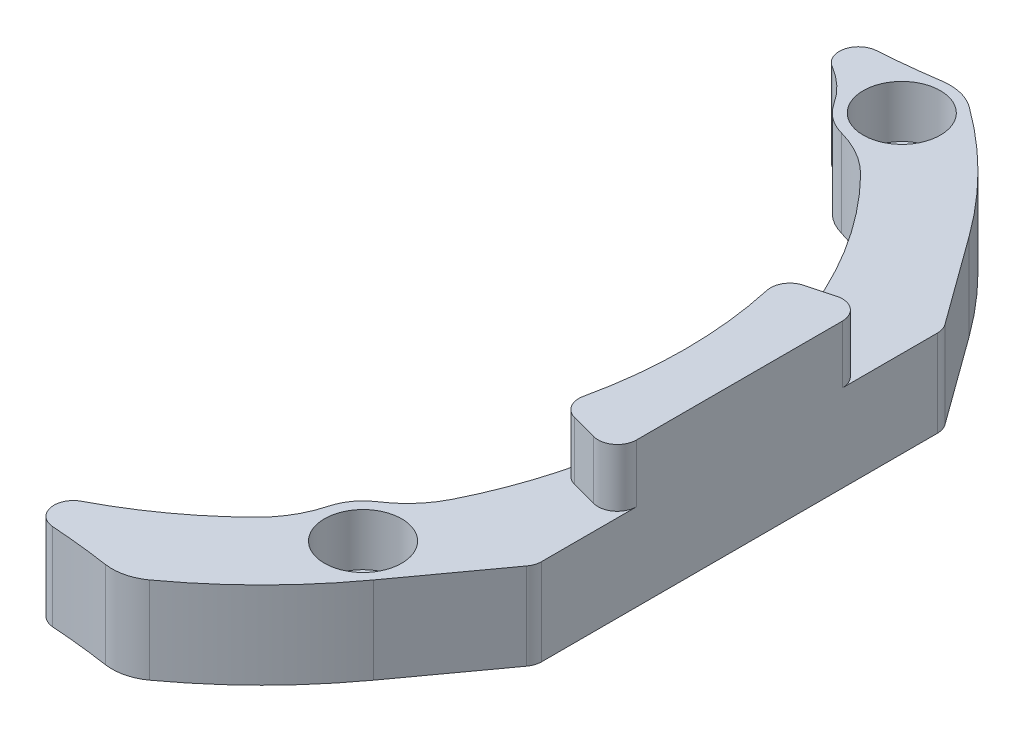
SolidWorks part; units mm, degrees
material "6061 合金"
ref_plane "前视基准面" through (0, 0, 0) normal (0, 0, 1) x (1, 0, 0)
ref_plane "上视基准面" through (0, 0, 0) normal (0, 1, 0) x (1, 0, 0)
ref_plane "右视基准面" through (0, 0, 0) normal (1, 0, 0) x (0, 0, -1)
other "Configuration Table"
sketch "草图1" plane through (0, 0, 0) normal (0, 1, 0) x (1, 0, 0)
  line L0 (0, 0) -> (36.1587, 0) construction
  arc A161 (21.6874, 13.5954) -> (21.2367, 15.4294) centre (19.2142, 13.9599) ccw construction
  arc A162 (21.6874, 13.5954) -> (21.5774, 2.7345) centre (61.26, 7.7635) ccw construction
  arc A163 (2.7345, 21.5774) -> (7.7635, 21.26) centre (7.7635, 61.26) ccw construction
  arc A164 (7.7635, 21.26) -> (13.5954, 21.6874) centre (7.7635, 61.26) ccw construction
  arc A165 (15.4294, 21.2367) -> (13.5954, 21.6874) centre (13.9599, 19.2142) ccw construction
  arc A166 (21.2367, 15.4294) -> (15.4294, 21.2367) centre (0, 0) ccw construction
  arc A167 (21.6874, 13.5954) -> (21.2367, 15.4294) centre (19.2142, 13.9599) ccw
  arc A168 (21.6874, 13.5954) -> (21.3486, 5.1029) centre (61.26, 7.7635) ccw
  arc A169 (5.1029, 21.3486) -> (7.7635, 21.26) centre (7.7635, 61.26) ccw
  arc A170 (7.7635, 21.26) -> (13.5954, 21.6874) centre (7.7635, 61.26) ccw
  arc A171 (15.4294, 21.2367) -> (13.5954, 21.6874) centre (13.9599, 19.2142) ccw
  arc A172 (21.2367, 15.4294) -> (15.4294, 21.2367) centre (0, 0) ccw
  circle A184 centre (13.9599, 19.2142) radius 1.025
  arc A212 (19.655, -9.7715) -> (15.6735, 15.367) centre (0, 0) ccw
  arc A213 (15.6735, 15.367) -> (13.302, 16.7505) centre (11.9604, 11.7265) ccw
  arc A214 (11.8201, 17.8271) -> (13.302, 16.7505) centre (13.9599, 19.2142) ccw
  arc A215 (11.8201, 17.8271) -> (9.7715, 19.655) centre (7.4566, 14.9987) ccw
  arc A216 (9.7715, 19.655) -> (-15.367, 15.6735) centre (0, 0) ccw
  arc A217 (21.3486, 5.1029) -> (15.6735, 15.367) centre (0, 0) ccw
  arc A218 (15.6735, 15.367) -> (13.302, 16.7505) centre (11.9604, 11.7265) ccw
  arc A219 (11.8201, 17.8271) -> (13.302, 16.7505) centre (13.9599, 19.2142) ccw
  arc A220 (11.8201, 17.8271) -> (9.7715, 19.655) centre (7.4566, 14.9987) ccw
  arc A221 (9.7715, 19.655) -> (5.1029, 21.3486) centre (0, 0) ccw
  arc A249 (13.5954, -21.6874) -> (13.9599, -21.7142) centre (13.9599, -19.2142) ccw construction
  arc A250 (13.5954, -21.6874) -> (2.7345, -21.5774) centre (7.7635, -61.26) ccw construction
  arc A251 (13.9599, -21.7142) -> (15.4294, -21.2367) centre (13.9599, -19.2142) ccw construction
  arc A252 (15.4294, -21.2367) -> (21.2367, -15.4294) centre (0, 0) ccw construction
  arc A253 (21.2367, -15.4294) -> (21.6874, -13.5954) centre (19.2142, -13.9599) ccw construction
  arc A254 (19.655, -9.7715) -> (15.6735, 15.367) centre (0, 0) ccw
  arc A255 (0, -21.95) -> (15.367, -15.6735) centre (0, 0) ccw
  arc A256 (15.367, -15.6735) -> (16.7505, -13.302) centre (11.7265, -11.9604) ccw
  arc A257 (17.8271, -11.8201) -> (16.7505, -13.302) centre (19.2142, -13.9599) ccw
  arc A258 (17.8271, -11.8201) -> (19.655, -9.7715) centre (14.9987, -7.4566) ccw
  arc A259 (19.655, -9.7715) -> (21.3486, -5.1029) centre (0, 0) ccw
  arc A260 (5.1029, -21.3486) -> (15.367, -15.6735) centre (0, 0) ccw
  arc A261 (15.367, -15.6735) -> (16.7505, -13.302) centre (11.7265, -11.9604) ccw
  arc A262 (17.8271, -11.8201) -> (16.7505, -13.302) centre (19.2142, -13.9599) ccw
  arc A263 (17.8271, -11.8201) -> (19.655, -9.7715) centre (14.9987, -7.4566) ccw
  arc A264 (21.5774, -2.7345) -> (21.6874, -13.5954) centre (61.26, -7.7635) ccw construction
  arc A265 (13.5954, -21.6874) -> (13.9599, -21.7142) centre (13.9599, -19.2142) ccw
  arc A266 (13.5954, -21.6874) -> (5.1029, -21.3486) centre (7.7635, -61.26) ccw
  arc A267 (13.9599, -21.7142) -> (15.4294, -21.2367) centre (13.9599, -19.2142) ccw
  arc A268 (15.4294, -21.2367) -> (21.2367, -15.4294) centre (0, 0) ccw
  arc A269 (21.2367, -15.4294) -> (21.6874, -13.5954) centre (19.2142, -13.9599) ccw
  arc A270 (21.3486, -5.1029) -> (21.6874, -13.5954) centre (61.26, -7.7635) ccw
  arc A271 (19.2142, -15.4099) -> (19.2142, -12.5099) centre (19.2142, -13.9599) ccw construction
  arc A272 (19.2142, -12.5099) -> (19.2142, -15.4099) centre (19.2142, -13.9599) ccw construction
  arc A273 (19.2142, -15.4099) -> (19.2142, -12.5099) centre (19.2142, -13.9599) ccw
  arc A274 (19.2142, -12.5099) -> (19.2142, -15.4099) centre (19.2142, -13.9599) ccw
  arc A275 (21.3486, 5.1029) -> (15.6735, 15.367) centre (0, 0) ccw
  dimension "D1" = 2.05
  dimension "D2" = 0.2
  dimension "D3" = 0.2
extrude "凸台-拉伸1" add sketch "草图1" along normal blind 4.5 contours A168 A167 A172 A171 A170 A169 A184 | A270 A259 A263 A262 A261 A260 A266 A265 A267 A268 A269 A274 A273 region at (16.4768, 0, -16.3777) region at (16.2264, 0, 16.6111)
sketch "草图4" plane through (0, 4.5, 0) normal (0, 1, 0) x (1, 0, 0)
  line L0 (0, 0) -> (32.7858, 0) construction
  line L1 (21.2367, -15.4294) -> (24.7634, -10.5753)
  line L2 (24.7634, -10.5753) -> (24.7634, 10.5753)
  line L3 (21.2367, 15.4294) -> (24.7634, 10.5753)
  arc A0 (21.6874, 13.5954) -> (21.2367, 15.4294) centre (19.2142, 13.9599) ccw construction
  arc A1 (21.2367, -15.4294) -> (21.6874, -13.5954) centre (19.2142, -13.9599) ccw construction
  arc A2 (21.6874, 13.5954) -> (21.3486, 5.1029) centre (61.26, 7.7635) ccw construction
  arc A3 (19.655, -9.7715) -> (15.6735, 15.367) centre (0, 0) ccw
  arc A4 (21.3486, -5.1029) -> (21.3486, 5.1029) centre (0, 0) ccw
  arc A5 (21.3486, -5.1029) -> (21.6874, -13.5954) centre (61.26, -7.7635) ccw construction
  arc A6 (21.6874, 13.5954) -> (21.3486, 5.1029) centre (61.26, 7.7635) ccw
  arc A7 (21.3486, -5.1029) -> (21.6874, -13.5954) centre (61.26, -7.7635) ccw
  arc A9 (21.6874, 13.5954) -> (21.2367, 15.4294) centre (19.2142, 13.9599) ccw
  arc A10 (21.2367, -15.4294) -> (21.6874, -13.5954) centre (19.2142, -13.9599) ccw
  point P16 (24.7634, 0)
  dimension "D2" = 6
  dimension "D1" = 0.2
extrude "凸台-拉伸2" add sketch "草图4" against normal up to surface (4.5 mm away) up to face at (19.2142, 0, 15.4099)
sketch "草图5" plane through (0, 4.5, 0) normal (0, 1, 0) x (1, 0, 0)
  line L0 (0, 0) -> (29.9967, 0) construction
  line L1 (21.2021, -5.6811) -> (24.7634, -6.6353)
  line L2 (24.7634, -10.5753) -> (24.7634, 10.5753) construction
  line L3 (21.2021, 5.6811) -> (24.7634, 6.6353)
  line L4 (24.7634, -6.6353) -> (24.7634, 6.6353)
  arc A0 (19.655, -9.7715) -> (15.6735, 15.367) centre (0, 0) ccw construction
  arc A1 (21.2021, -5.6811) -> (21.2021, 5.6811) centre (0, 0) ccw
  dimension "D1" = 15
extrude "凸台-拉伸3" add sketch "草图5" along normal blind 3
sketch "草图6" plane through (0, 7.5, 0) normal (0, 1, 0) x (1, 0, 0)
  line L0 (24.7634, -6.6353) -> (18.3043, -4.9046)
  line L1 (24.7634, 6.6353) -> (18.3043, 4.9046)
  line L2 (24.7634, -6.6353) -> (24.7634, 6.6353)
  arc A2 (18.3043, -4.9046) -> (18.3043, 4.9046) centre (0, 0) ccw
  arc A3 (18.3043, -4.9046) -> (18.3043, 4.9046) centre (0, 0) ccw
  dimension "D1" = 3
extrude "凸台-拉伸4" [suppressed] add sketch "草图6" against normal blind 3
fillet "圆角2" [suppressed] radius 1
sketch "草图7" plane through (0, 4.5, 0) normal (0, 1, 0) x (1, 0, 0)
  circle A0 centre (19.2142, -13.9599) radius 1
  circle A1 centre (19.2142, -13.9599) radius 1.45 construction
  circle A2 centre (19.2142, -13.9599) radius 1.45
  dimension "D1" = 2
extrude "凸台-拉伸5" add sketch "草图7" against normal up to surface (4.5 mm away) up to face at (15.8728, 0, -1.0637)
hole_wizard "M2.5 六角圆柱头螺钉的柱形沉头孔2" positions "3D草图3" profile "草图12" counterbore size "M2.5" standard "GB" end condition through all
sketch3d "3D草图3"
  line L0 (13.9599, 4.5, -19.2142) -> (13.9599, 0, -19.2142) construction
  line L1 (19.2142, 0, 13.9599) -> (19.2142, 4.5, 13.9599) construction
  point P0 (13.9599, 4.5, -19.2142)
  point P4 (19.2142, 4.5, 13.9599)
sketch "草图12" plane through (13.9599, 4.5, -19.2142) normal (1, 0, 0) x (0, 0, 1)
  line L0 (0, 0) -> (0, 4.5)
  line L1 (0, 4.5) -> (1.45, 4.5)
  line L3 (1.45, 4.5) -> (1.45, 2.7)
  line L4 (1.45, 2.7) -> (2, 2.7)
  line L5 (2, 2.7) -> (2, 0)
  line L7 (2, 0) -> (0, 0)
  line L11 (0, -6.35) -> (0, 107.95) construction
  dimension "通孔孔直径" = 2.9
  dimension "通孔孔深度" = 4.5
  dimension "柱形沉头孔直径" = 4
  dimension "柱形沉头孔深度" = 2.7
fillet "圆角5" radius 1 8 edges at (24.7634, 2.25, 10.5753) (24.7634, 2.25, -10.5753) (24.7634, 6, -6.6353) (21.2021, 6, -5.6811) (21.2021, 6, 5.6811) (24.7634, 6, 6.6353) (5.1029, 2.25, 21.3486) (5.1029, 2.25, -21.3486)
